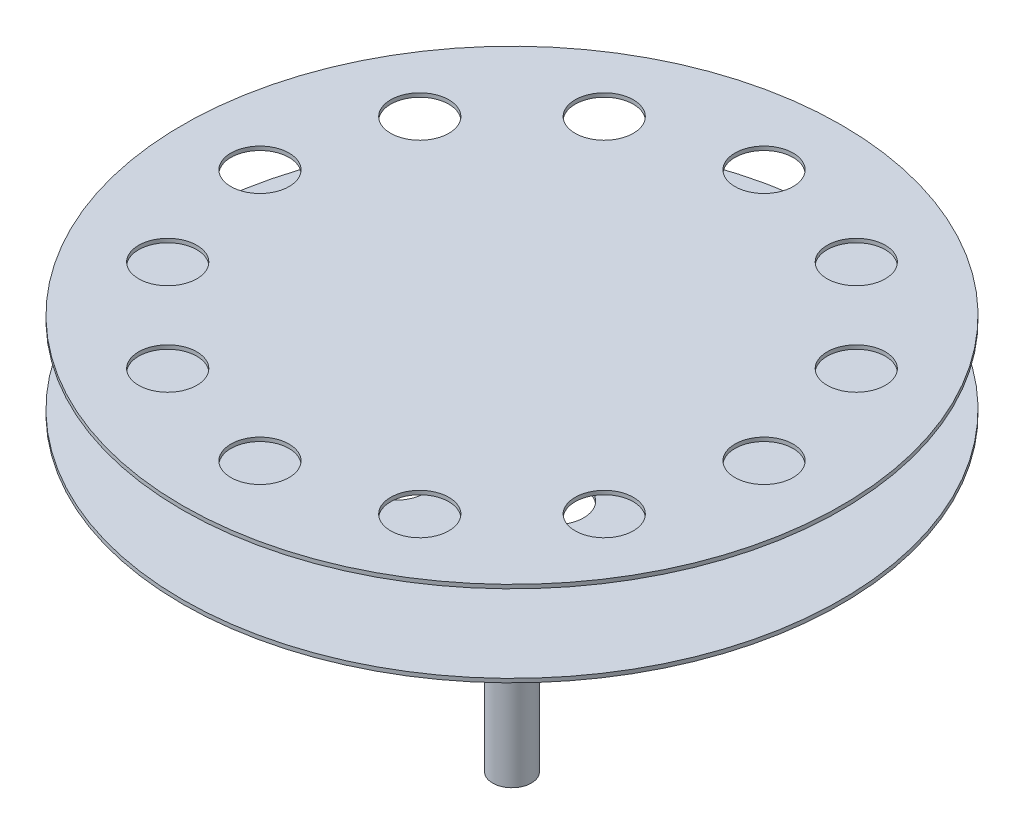
SolidWorks part; units mm, degrees
ref_plane "Front Plane" through (0, 0, 0) normal (0, 0, 1) x (1, 0, 0)
ref_plane "Top Plane" through (0, 0, 0) normal (0, 1, 0) x (1, 0, 0)
ref_plane "Right Plane" through (0, 0, 0) normal (1, 0, 0) x (0, 0, -1)
sketch "Sketch1" plane through (0, 0, 0) normal (0, 0, 1) x (1, 0, 0)
  line L0 (0, 0) -> (0, 52.2611) construction
  line L1 (0, 102) -> (-84.9998, 102)
  line L2 (-84.9998, 102) -> (-84.9998, 101)
  line L3 (-84.9998, 101) -> (-5, 101)
  line L4 (-5, 101) -> (-5, 81)
  line L5 (-5, 81) -> (-84.9998, 81)
  line L6 (-84.9998, 81) -> (-84.9998, 80)
  line L7 (-84.9998, 80) -> (-5, 80)
  line L8 (-5, 80) -> (-5, 0)
  line L9 (-5, 0) -> (0, 0)
  line L10 (0, 0) -> (0, 102)
  line L11 (-5, 81) -> (-5, 80) construction
  line L12 (-84.9998, 101) -> (-84.9998, 81) construction
  dimension "D1" = 84.9998
  dimension "D2" = 1
  dimension "D3" = 20
  dimension "D4" = 5
  dimension "D5" = 80
ref_axis "Axis1" through (0, 54.8742, 0) along (0, -1, 0)
revolve "Revolve1" add sketch "Sketch1" angle 360 about axis through (0, 54.8742, 0) along (0, -1, 0)
sketch "Sketch2" plane through (0, 102, 0) normal (0, 1, 0) x (1, 0, 0)
  line L0 (0, 0) -> (0, 65) construction
  circle A0 centre (0, 65) radius 7.5
  dimension "D1" = 15
  dimension "D2" = 65
extrude "Cut-Extrude1" cut sketch "Sketch2" against normal blind 2
pattern_circular "CirPattern1" count 12 over 360 about axis through (0, 54.8742, 0) along (0, -1, 0) of "Cut-Extrude1"
sketch "Sketch3" plane through (0, 80, 0) normal (0, -1, 0) x (1, 0, 0)
  line L0 (0, 0) -> (0, 30) construction
  circle A0 centre (0, 30) radius 7.5
  dimension "D2" = 15
  dimension "D1" = 30
extrude "Cut-Extrude2" cut sketch "Sketch3" against normal blind 2
pattern_circular "CirPattern2" count 6 over 360 about axis through (0, 54.8742, 0) along (0, -1, 0) of "Cut-Extrude2"
equation "\"TubeDiameter\" = 6.6929in"
equation "\"D1@Sketch1\"=\"TubeDiameter\"/2"
